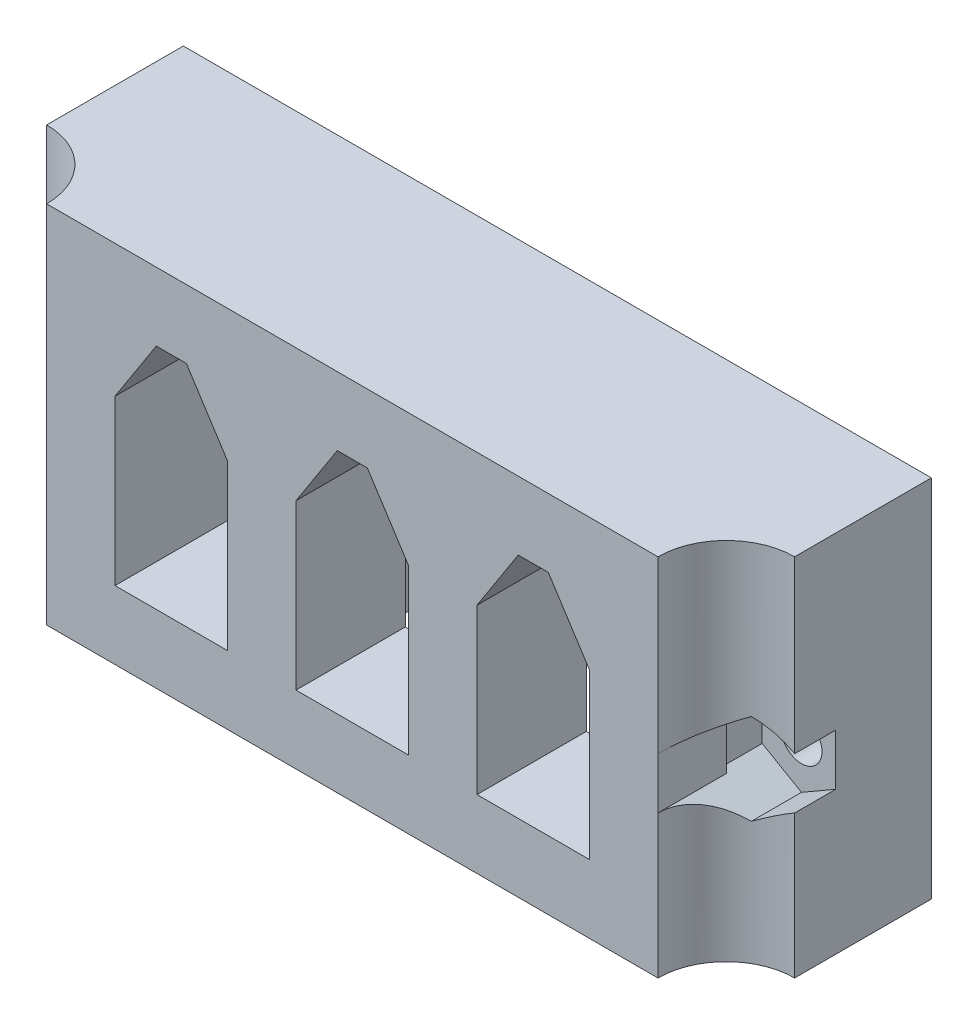
SolidWorks part; units mm, degrees
ref_plane "Front" through (0, 0, 0) normal (0, 0, 1) x (1, 0, 0)
ref_plane "Top" through (0, 0, 0) normal (0, 1, 0) x (1, 0, 0)
ref_plane "Right" through (0, 0, 0) normal (1, 0, 0) x (0, 0, -1)
sketch "Sketch1" plane through (0, 0, 0) normal (0, 0, 1) x (1, 0, 0)
  line L0 (0, 0) -> (0, 12)
  line L1 (0, 12) -> (3.02, 16.686)
  line L3 (8.24, 12) -> (8.24, 0)
  line L4 (0, 0) -> (8.24, 0)
  line L5 (3.02, 16.686) -> (5.22, 16.686)
  line L6 (5.22, 16.686) -> (8.24, 12)
  line L7 (18.46, 16.686) -> (21.48, 12)
  line L8 (21.48, 12) -> (21.48, 0)
  line L9 (13.24, 0) -> (21.48, 0)
  line L10 (13.24, 0) -> (13.24, 12)
  line L11 (13.24, 12) -> (16.26, 16.686)
  line L12 (16.26, 16.686) -> (18.46, 16.686)
  line L13 (31.7, 16.686) -> (34.72, 12)
  line L14 (34.72, 12) -> (34.72, 0)
  line L15 (26.48, 0) -> (34.72, 0)
  line L16 (26.48, 0) -> (26.48, 12)
  line L17 (26.48, 12) -> (29.5, 16.686)
  line L18 (29.5, 16.686) -> (31.7, 16.686)
  line L26 (-10, -5) -> (44.72, -5)
  line L27 (-10, -5) -> (-10, 21.686)
  line L28 (-10, 21.686) -> (44.72, 21.686)
  line L29 (44.72, -5) -> (44.72, 21.686)
  point P9 (4.12, 16.686)
  point P10 (4.12, 0)
  point P25 (17.36, 0)
  point P26 (17.36, -5)
  dimension "D1" = 8.24
  dimension "D2" = 16.686
  dimension "D3" = 2.2
  dimension "D4" = 12
  dimension "D6" = 5
  dimension "D7" = 5
  dimension "D8" = 5
  dimension "D9" = 10
  dimension "D5" = 3
extrude "Boss-Extrude1" add sketch "Sketch1" along normal blind 15
sketch "Sketch2" plane through (0, -5, 0) normal (0, -1, 0) x (-1, 0, 0)
  line L0 (-17.36, -15) -> (-17.36, 0) construction
  line L1 (10, -15) -> (-44.72, -15) construction
  line L2 (10, 0) -> (-44.72, 0) construction
  line L3 (-44.72, -15) -> (-44.72, 0) construction
  line L4 (10, -15) -> (5, -15)
  line L5 (10, -15) -> (10, -10)
  line L6 (10, -10) -> (5, -10)
  line L7 (5, -15) -> (5, -10)
  line L8 (-39.72, -15) -> (-44.72, -15)
  line L9 (-39.72, -15) -> (-39.72, -10)
  line L10 (-39.72, -10) -> (-44.72, -10)
  line L11 (-44.72, -15) -> (-44.72, -10)
  point P19 (0, 0)
  dimension "D1" = 5
  dimension "D2" = 10
extrude "Cut-Extrude1" cut sketch "Sketch2" against normal through all
sketch "Sketch3" plane through (0, 0, 10) normal (0, 0, 1) x (1, 0, 0)
  line L0 (-10, 21.686) -> (-5, 21.686) construction
  line L1 (39.72, 21.686) -> (44.72, 21.686) construction
  circle A0 centre (-7.5, 7.3315) radius 1.5
  circle A1 centre (42.22, 7.3315) radius 1.5
  point P4 (0, 0)
  point P5 (0, 0)
  point P8 (-7.5, 21.686)
  point P9 (0, 0)
  point P12 (42.22, 21.686)
  dimension "D1" = 3
extrude "Cut-Extrude2" cut sketch "Sketch3" against normal blind 25
sketch "Sketch4" plane through (0, 0, 10) normal (0, 0, 1) x (1, 0, 0)
  line L1 (-7.5, 10.6513) -> (-10.375, 8.9914)
  line L2 (-10.375, 8.9914) -> (-10.375, 5.6716)
  line L3 (-10.375, 5.6716) -> (-7.5, 4.0117)
  line L4 (-7.5, 4.0117) -> (-4.625, 5.6716)
  line L5 (-4.625, 5.6716) -> (-4.625, 8.9914)
  line L6 (-4.625, 8.9914) -> (-7.5, 10.6513)
  line L7 (42.22, 10.6513) -> (39.345, 8.9914)
  line L8 (39.345, 8.9914) -> (39.345, 5.6716)
  line L9 (39.345, 5.6716) -> (42.22, 4.0117)
  line L10 (42.22, 4.0117) -> (45.095, 5.6716)
  line L11 (45.095, 5.6716) -> (45.095, 8.9914)
  line L12 (45.095, 8.9914) -> (42.22, 10.6513)
  circle A0 centre (-7.5, 7.3315) radius 2.875 construction
  circle A1 centre (42.22, 7.3315) radius 2.875 construction
  point P10 (-4.625, 7.3315)
  dimension "D1" = 5.75
extrude "Cut-Extrude3" cut sketch "Sketch4" against normal blind 3
sketch "Sketch5" plane through (0, -5, 0) normal (0, -1, 0) x (1, 0, 0)
  line L0 (-10, 0) -> (44.72, 0) construction
  line L1 (0, 7) -> (34.72, 7)
  line L2 (0, 7) -> (0, 0)
  line L3 (0, 0) -> (34.72, 0)
  line L4 (34.72, 7) -> (34.72, 0)
  line L5 (-5, 15) -> (39.72, 15) construction
  dimension "D1" = 8
sketch "Sketch7" plane through (0, 0, 0) normal (0, 0, -1) x (-1, 0, 0)
  line L0 (-34.72, 0) -> (-34.72, 12) construction
  line L1 (0, 0) -> (-7.36, 0)
  line L2 (0, 0) -> (0, 16.686)
  line L3 (0, 16.686) -> (-34.72, 16.686)
  line L4 (-34.72, 0) -> (-34.72, 16.686)
  line L5 (-31.7, 16.686) -> (-29.5, 16.686) construction
  line L6 (0, -5) -> (-34.72, -5) construction
  line L7 (-7.36, -5) -> (-27.36, -5)
  line L8 (-7.36, -5) -> (-7.36, 0)
  line L10 (-27.36, -5) -> (-27.36, 0)
  line L11 (-27.36, 0) -> (-34.72, 0)
  point P15 (-17.36, -5)
  point P16 (-17.36, 16.686)
  dimension "D1" = 20
extrude "Cut-Extrude5" cut sketch "Sketch7" against normal blind 7
fillet "Fillet2" radius 5 4 edges at (-5, 0.2276, 10) (-5, 15.4469, 10) (39.72, 15.4469, 10) (39.72, 0.2276, 10)
